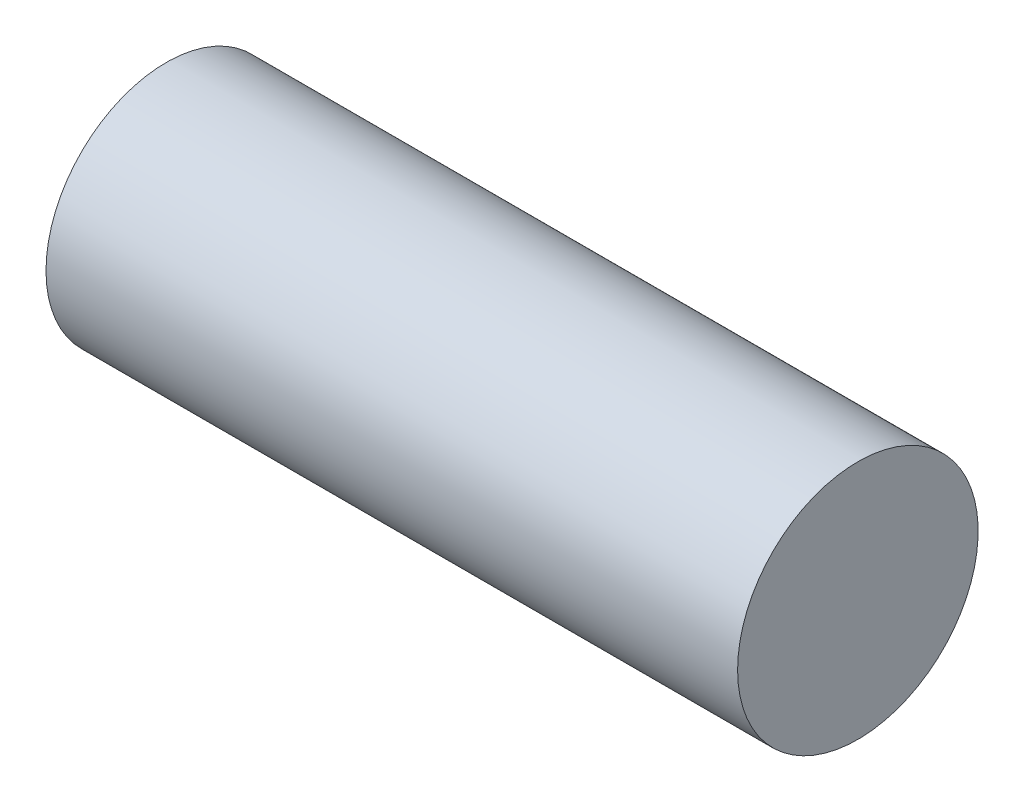
SolidWorks part; units mm, degrees
ref_plane "Front Plane" through (0, 0, 0) normal (0, 0, 1) x (1, 0, 0)
ref_plane "Top Plane" through (0, 0, 0) normal (0, 1, 0) x (1, 0, 0)
ref_plane "Right Plane" through (0, 0, 0) normal (1, 0, 0) x (0, 0, -1)
sketch "Sketch2" plane through (0, 0, 0) normal (0, 0, 1) x (1, 0, 0)
  line L0 (-9.1559, 0) -> (-2.2559, 0)
  line L1 (-2.2559, 0) -> (-2.2559, 1.2)
  line L2 (-2.2559, 1.2) -> (-9.1559, 1.2)
  line L3 (-9.1559, 1.2) -> (-9.1559, 0)
  dimension "D1" = 1.2
  dimension "D2" = 6.9
revolve "Revolve1" add sketch "Sketch2" angle 360 about L0
